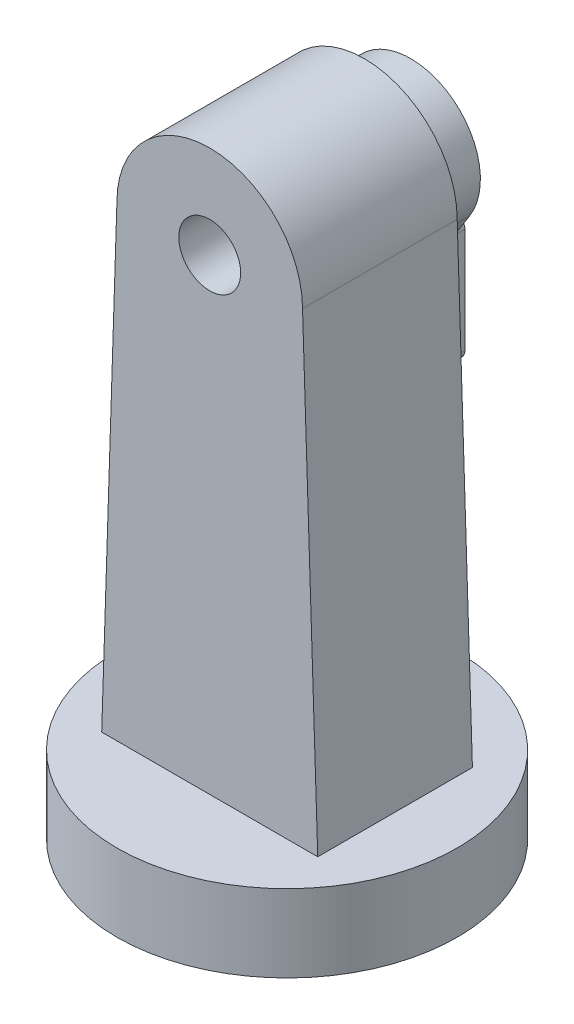
SolidWorks part; units mm, degrees
material "Acier non allié"
ref_plane "Plan de face" through (0, 0, 0) normal (0, 0, 1) x (1, 0, 0)
ref_plane "Plan de dessus" through (0, 0, 0) normal (0, 1, 0) x (1, 0, 0)
ref_plane "Plan de droite" through (0, 0, 0) normal (1, 0, 0) x (0, 0, -1)
sketch "Esquisse1" plane through (0, 0, 0) normal (0, 1, 0) x (1, 0, 0)
  circle A0 centre (0, 0) radius 110
  dimension "D1" = 220
extrude "Boss.-Extru.1" add sketch "Esquisse1" along normal blind 50
sketch "Esquisse2" plane through (0, 0, 0) normal (0, 0, 1) x (1, 0, 0)
  line L0 (0, 0) -> (0, 352) construction
  line L1 (-70, 45) -> (70, 45)
  line L2 (70, 45) -> (60, 352)
  line L3 (-60, 352) -> (-70, 45)
  arc A0 (60, 352) -> (-60, 352) centre (0, 352) ccw
  dimension "D4" = 60
  dimension "D1" = 140
  dimension "D2" = 45
  dimension "D3" = 352
  dimension "D5" = 120
extrude "Boss.-Extru.2" add sketch "Esquisse2" along normal mid plane 100
sketch "Esquisse3" plane through (0, 0, 50) normal (0, 0, 1) x (1, 0, 0)
  line L0 (0, 0) -> (0, 352) construction
  circle A0 centre (0, 352) radius 20
  dimension "D2" = 40
  dimension "D1" = 352
extrude "Enlèv. mat.-Extru.1" cut sketch "Esquisse3" against normal through all
sketch "Esquisse4" plane through (0, 0, -50) normal (0, 0, -1) x (-1, 0, 0)
  line L0 (0, 0) -> (0, 352) construction
  line L1 (0, 200) -> (90, 200) construction
  line L2 (-38.0569, 327.986) -> (56.1716, 178.6543)
  line L3 (124.9821, 219.3973) -> (39.3548, 373.8219)
  arc A0 (39.3548, 373.8219) -> (-38.0569, 327.986) centre (0, 352) ccw
  arc A1 (56.1716, 178.6543) -> (124.9821, 219.3973) centre (90, 200) ccw
  dimension "D4" = 45
  dimension "D5" = 40
  dimension "D1" = 352
  dimension "D2" = 90
  dimension "D3" = 200
extrude "Boss.-Extru.3" add sketch "Esquisse4" along normal blind 30
sketch "Esquisse5" plane through (0, 0, -80) normal (0, 0, -1) x (-1, 0, 0)
  line L0 (0, 0) -> (0, 200) construction
  line L1 (0, 200) -> (90, 200) construction
  line L3 (56, 160) -> (124, 160)
  line L4 (50, 166) -> (50, 234)
  line L5 (56, 240) -> (124, 240)
  line L6 (130, 166) -> (130, 234)
  line L7 (50, 160) -> (130, 240) construction
  line L8 (50, 240) -> (130, 160) construction
  arc A0 (56, 160) -> (50, 166) centre (56, 166) cw
  arc A1 (124, 160) -> (130, 166) centre (124, 166) ccw
  arc A2 (50, 234) -> (56, 240) centre (56, 234) cw
  arc A3 (124, 240) -> (130, 234) centre (124, 234) cw
  dimension "D5" = 6
  dimension "D6" = 6
  dimension "D7" = 6
  dimension "D8" = 6
  dimension "D1" = 200
  dimension "D2" = 90
  dimension "D3" = 80
  dimension "D4" = 80
extrude "Boss.-Extru.4" add sketch "Esquisse5" along normal blind 85
ref_axis "Axis_J1" through (0, 50, 0) along (0, -1, 0)
ref_axis "Axis_J2" through (0, 352, -50) along (0, 0, 1)
